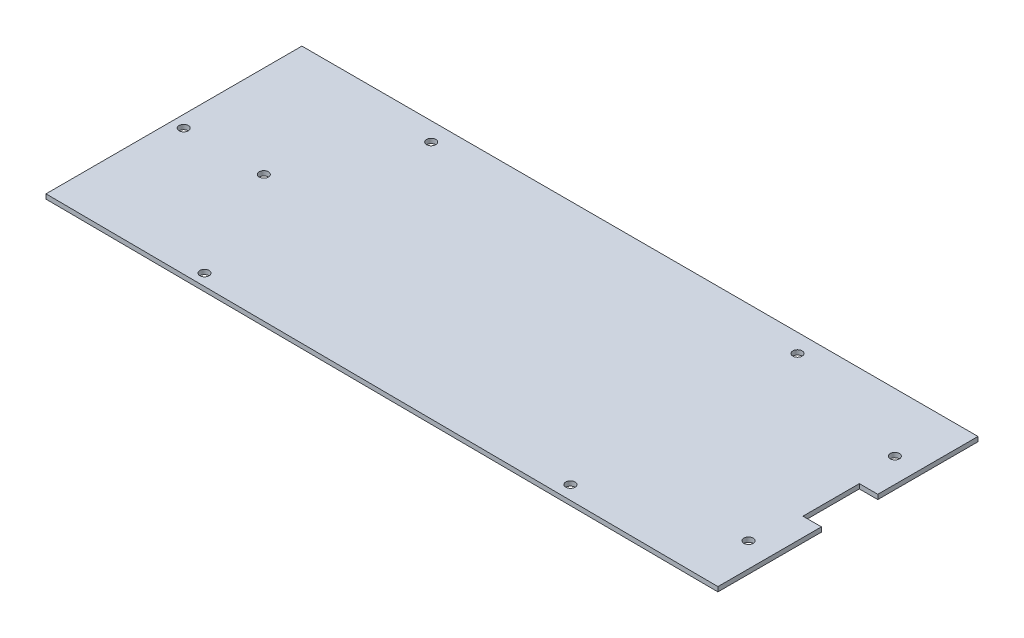
SolidWorks part; units mm, degrees
ref_plane "Front Plane" through (0, 0, 0) normal (0, 0, 1) x (1, 0, 0)
ref_plane "Top Plane" through (0, 0, 0) normal (0, 1, 0) x (1, 0, 0)
ref_plane "Right Plane" through (0, 0, 0) normal (1, 0, 0) x (0, 0, -1)
sketch "Sketch1" plane through (0, 0, 0) normal (0, 1, 0) x (1, 0, 0)
  line L13 (56.0007, -497.9804) -> (495.3335, -497.9804)
  line L21 (56.0007, -664.2568) -> (495.3335, -666.9835)
  line L22 (495.3335, -497.9804) -> (495.3335, -563.091)
  line L25 (495.3335, -563.091) -> (483.3335, -563.091)
  line L33 (483.3335, -563.091) -> (483.3335, -599.7266)
  line L34 (483.3335, -599.7266) -> (495.3335, -599.7266)
  line L36 (495.3335, -599.7266) -> (495.3335, -666.9835)
  line L38 (56.0007, -497.9804) -> (56.0007, -664.2568)
  circle A12 centre (63.7956, -582.5636) radius 3
  circle A13 centre (115.8464, -582.5636) radius 3
  circle A14 centre (152.0145, -509.9557) radius 3
  circle A15 centre (152.1131, -657.3773) radius 3
  circle A16 centre (390.0145, -657.4936) radius 3
  circle A17 centre (479.4749, -631.2236) radius 3
  circle A18 centre (479.4225, -536.1177) radius 3
  circle A19 centre (390.0145, -509.9557) radius 3
  point P4 (0, 0)
  point P5 (272.5206, -582.4819)
  point P24 (49.7077, -664.2177)
  dimension "D9" = 8.8361
  dimension "D12" = 15.8586
  dimension "D15" = 11.9753
  dimension "D16" = 105.319
  dimension "D18" = 6
  dimension "D6" = 84.5832
  dimension "D17" = 6
  dimension "D21" = 6
  dimension "D22" = 6
  dimension "D23" = 6
  dimension "D24" = 6
  dimension "D4" = 11.9753
  dimension "D10" = 105.319
  dimension "D11" = 35.6608
  dimension "D13" = 15.911
  dimension "D14" = 38.1373
extrude "Boss-Extrude1" add sketch "Sketch1" along normal blind 3
